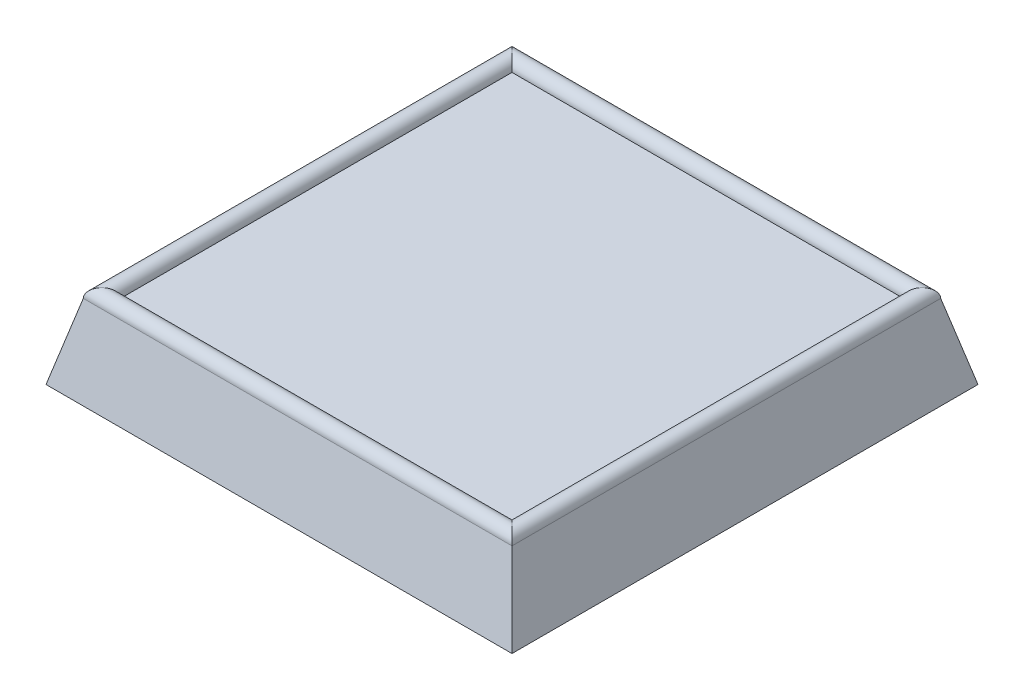
SolidWorks part; units mm, degrees
ref_plane "前视基准面" through (0, 0, 0) normal (0, 0, 1) x (1, 0, 0)
ref_plane "上视基准面" through (0, 0, 0) normal (0, 1, 0) x (1, 0, 0)
ref_plane "右视基准面" through (0, 0, 0) normal (1, 0, 0) x (0, 0, -1)
sketch "草图2" plane through (0, 0, 0) normal (0, 1, 0) x (1, 0, 0)
  line L0 (-115, -115) -> (-115, 115)
  line L1 (-105, -105) -> (105, -105) construction
  line L2 (-105, -105) -> (-105, 105) construction
  line L3 (-105, 105) -> (105, 105) construction
  line L4 (105, -105) -> (105, 105) construction
  line L5 (-105, -105) -> (105, 105) construction
  line L6 (-105, 105) -> (105, -105) construction
  line L7 (-115, 115) -> (115, 115)
  line L8 (115, -115) -> (115, 115)
  line L9 (-115, -115) -> (115, -115)
  line L10 (-125, -125) -> (-125, 125) construction
  line L11 (-125, 125) -> (125, 125) construction
  line L12 (125, -125) -> (125, 125) construction
  line L13 (-125, -125) -> (125, -125) construction
  point P0 (0, 0)
  dimension "D1" = 210
  dimension "D2" = 210
  dimension "D3" = 10
  dimension "D4" = 10
ref_plane "基准面4" through (0, -40, 0) normal (0, 1, 0) x (1, 0, 0)
sketch "草图3" plane through (0, -40, 0) normal (0, 1, 0) x (1, 0, 0)
  line L0 (125, -125) -> (125, 125) construction
  line L1 (-125, -125) -> (125, -125) construction
  line L2 (-125, -125) -> (-125, 125) construction
  line L3 (-125, 125) -> (125, 125) construction
  line L4 (125, -125) -> (125, 125)
  line L5 (-125, -125) -> (125, -125)
  line L6 (-125, -125) -> (-125, 125)
  line L7 (-125, 125) -> (125, 125)
loft "放样1" add profiles "草图2", "草图3" connector at (-115, 0, -115) connector at (-125, -40, -125)
ref_plane "基准面5" through (0, 0, 115) normal (0, 0, -1) x (-1, 0, 0)
sketch "草图4" plane through (0, 0, 115) normal (0, 0, -1) x (-1, 0, 0)
  line L0 (-115, 0) -> (-105, 0)
  arc A0 (-105, 0) -> (-115, 0) centre (-110, 0) ccw
  point P0 (-105, 0)
  point P2 (-115, 0)
sweep "扫描1" add profiles "草图4" path "草图2<2>"
sketch "草图2<2>" plane through (0, 0, 0) normal (0, 1, 0) x (1, 0, 0) same geometry as "草图2"
